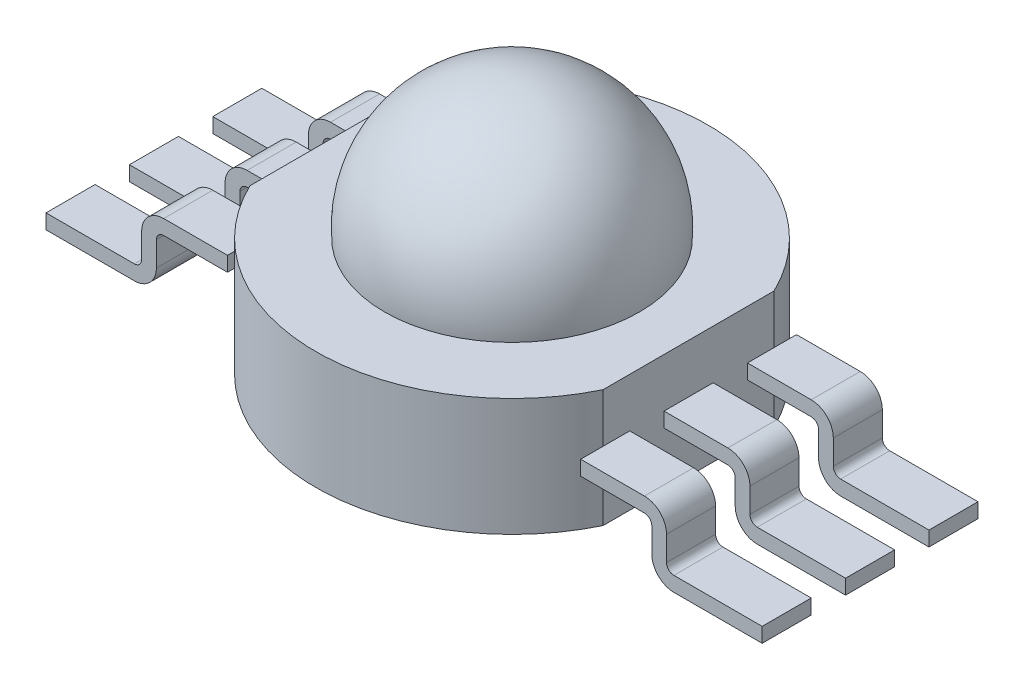
SolidWorks part; units mm, degrees
material "ABS"
ref_plane "Front Plane" through (0, 0, 0) normal (0, 0, 1) x (1, 0, 0)
ref_plane "Top Plane" through (0, 0, 0) normal (0, 1, 0) x (1, 0, 0)
ref_plane "Right Plane" through (0, 0, 0) normal (1, 0, 0) x (0, 0, -1)
sketch "Sketch1" plane through (0, 0, 0) normal (0, 1, 0) x (1, 0, 0)
  line L0 (-3.6, 1.7436) -> (-3.6, -1.7436)
  line L1 (3.6, 1.7436) -> (3.6, -1.7436)
  arc A0 (3.6, 1.7436) -> (-3.6, 1.7436) centre (0, 0) ccw
  arc A1 (-3.6, -1.7436) -> (3.6, -1.7436) centre (0, 0) ccw
  dimension "D1" = 8
  dimension "D2" = 7.2
extrude "LED Base Boss-Extrude1" add sketch "Sketch1" along normal blind 2.4
sketch "Sketch3" plane through (0, 0, 0) normal (0, 0, 1) x (1, 0, 0)
  line L0 (0, 0) -> (0, 5.0961) construction
  line L1 (3.6, 2.4) -> (-3.6, 2.4) construction
  line L2 (0, 5.2) -> (2.6, 5.2) construction
  line L3 (2.6, 2.4) -> (2.6, 5.2) construction
  line L4 (2.6, 2.4) -> (0, 2.4)
  line L5 (0, 5.2) -> (0, 2.4)
  arc A0 (0, 5.2) -> (2.6, 2.4) centre (0, 2.5929) cw
  dimension "D1" = 2.6
  dimension "D2" = 5.2
revolve "LED Lens Revolve2" add sketch "Sketch3" angle 360 about L5
sketch "Sketch4" plane through (0, 0, 0) normal (0, 0, 1) x (1, 0, 0)
  line L0 (3.6, 2.4) -> (3.6, 0) construction
  line L1 (3.6, 1.4) -> (4.9, 1.4)
  line L2 (3.6, 1.4) -> (3.6, 1.1)
  line L3 (3.6, 1.1) -> (4.9, 1.1)
  line L4 (5.05, 0.95) -> (5.05, 0.45)
  line L5 (5.35, 0.95) -> (5.35, 0.45)
  line L6 (4.9, 1.4) -> (4.9, 1.1) construction
  line L7 (5.5, 0.3) -> (5.5, 0) construction
  line L8 (5.05, 0.7) -> (5.35, 0.7) construction
  line L9 (-3.6, 0) -> (3.6, 0) construction
  line L10 (5.5, 0) -> (7.3, 0)
  line L12 (5.5, 0.3) -> (7.3, 0.3)
  line L13 (7.3, 0) -> (7.3, 0.3)
  arc A0 (4.9, 1.4) -> (5.35, 0.95) centre (4.9, 0.95) cw
  arc A1 (4.9, 1.1) -> (5.05, 0.95) centre (4.9, 0.95) cw
  arc A2 (5.05, 0.45) -> (5.5, 0) centre (5.5, 0.45) ccw
  arc A3 (5.35, 0.45) -> (5.5, 0.3) centre (5.5, 0.45) ccw
  dimension "D1" = 3.7
  dimension "D2" = 0.3
  dimension "D3" = 1.4
  dimension "D4" = 0
  dimension "D5" = 0.5
  dimension "D6" = 1.3
  dimension "D7" = 1.8
extrude "Pin Right Boss-Extrude2" add sketch "Sketch4" along normal blind 2.2 and the other way blind 2.2
sketch "Sketch5" plane through (0, 1.4, 0) normal (0, 1, 0) x (1, 0, 0)
  line L0 (3.6, -1.7436) -> (3.6, 1.7436) construction
  line L1 (3.6, 1.2) -> (7.3, 1.2)
  line L2 (3.6, 1.2) -> (3.6, 0.5)
  line L3 (3.6, 0.5) -> (7.3, 0.5)
  line L4 (7.3, 1.2) -> (7.3, 0.5)
  line L5 (7.3, 2.2) -> (7.3, -2.2) construction
  line L6 (0, 0) -> (1.3969, 0) construction
  line L7 (7.3, -0.5) -> (3.6, -0.5)
  line L8 (7.3, -0.5) -> (7.3, -1.2)
  line L9 (7.3, -1.2) -> (3.6, -1.2)
  line L10 (3.6, -0.5) -> (3.6, -1.2)
  line L11 (3.6, -0.5) -> (3.6, 0) construction
  line L12 (3.6, 1.7436) -> (3.6, -1.7436) construction
  line L13 (3.6, 0) -> (3.6, 0.5) construction
  line L14 (7.3, 2.2) -> (7.3, 1.2) construction
  line L15 (7.3, 0.5) -> (7.3, -0.5) construction
  line L16 (7.3, -1.2) -> (7.3, -2.2) construction
  line L17 (7.3, 2.2) -> (5.5, 2.2) construction
  dimension "D1" = 0.7
  dimension "D2" = 1
  dimension "D3" = 4.4
extrude "Pin Right Space Cut-Extrude1" cut sketch "Sketch5" against normal up to surface (1.4 mm away) up to face at (6.4, 0, 0)
mirror "Pin Left Mirror1" about plane through (0, 0, 0) normal (1, 0, 0) of "Pin Right Space Cut-Extrude1", "Pin Right Boss-Extrude2"
sketch "Sketch6" plane through (0, 0, 0) normal (0, -1, 0) x (1, 0, 0)
  circle A0 centre (0, 0) radius 2.7
  dimension "D1" = 5.4
extrude "Heatsink Boss-Extrude3" add sketch "Sketch6" along normal blind 0.1
equation "\"D1@Sketch3\"=5.2/2"
equation "\"D1@Sketch4\"=(14.60-7.2)/2"
equation "\"D1@Pin Right Boss-Extrude2\"=(1+0.7+1+0.7+1)/2"
equation "\"D2@Pin Right Boss-Extrude2\"=(1+0.7+1+0.7+1)/2"
